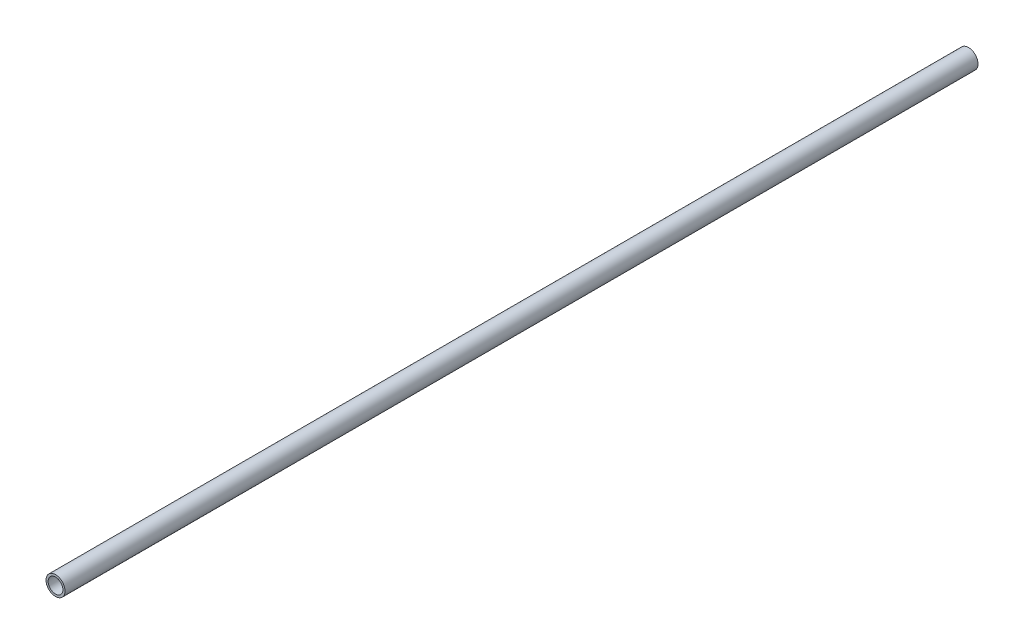
SolidWorks part; units mm, degrees
ref_plane "Front Plane" through (0, 0, 0) normal (0, 0, 1) x (1, 0, 0)
ref_plane "Top Plane" through (0, 0, 0) normal (0, 1, 0) x (1, 0, 0)
ref_plane "Right Plane" through (0, 0, 0) normal (1, 0, 0) x (0, 0, -1)
sketch "Sketch1" plane through (0, 0, 0) normal (0, 0, 1) x (1, 0, 0)
  line L0 (-3.175, 0) -> (3.175, 0) construction
  line L1 (0, 0) -> (0, 1.0456) construction
  point P0 (-2.4638, 0)
  point P4 (0, 0)
  point P6 (2.4638, 0)
  dimension "OD" = 6.35
  dimension "ID" = 4.9276
sketch "Sketch2" plane through (0, 0, 0) normal (0, 0, 1) x (1, 0, 0)
  line L0 (-3.175, 0) -> (3.175, 0) construction
  circle A0 centre (0, 0) radius 2.4638
  circle A1 centre (0, 0) radius 3.175
  dimension "D1" = 4.9276
  dimension "D2" = 6.35
extrude "Boss-Extrude1" add sketch "Sketch2" along normal mid plane 304.8
sketch "Sketch3" plane through (0, 0, 0) normal (1, 0, 0) x (0, 0, -1)
  line L0 (152.4, 0) -> (-152.4, 0) construction
  line L1 (-152.4, 3.175) -> (-152.4, -3.175) construction
  line L2 (0, 0) -> (0, 21.8825) construction
  point P0 (-150.876, 0)
  point P6 (0, 0)
  point P8 (150.876, 0)
  dimension "D1" = 301.752
ref_axis "Center Axis 1" through (0, 0, 152.4) along (0, 0, -1)
ref_plane "Contact Plane 1" through (0, 0, 152.4) normal (0, 0, 1) x (1, 0, 0)
ref_plane "Contact Plane 2" through (0, 0, -152.4) normal (0, 0, -1) x (-1, 0, 0)
equation "\"D1@Sketch2\"=\"ID@Sketch1\""
equation "\"D2@Sketch2\"=\"OD@Sketch1\""
equation "\"D1@Sketch3\"=\"Length@Boss-Extrude1\"*0.99"
